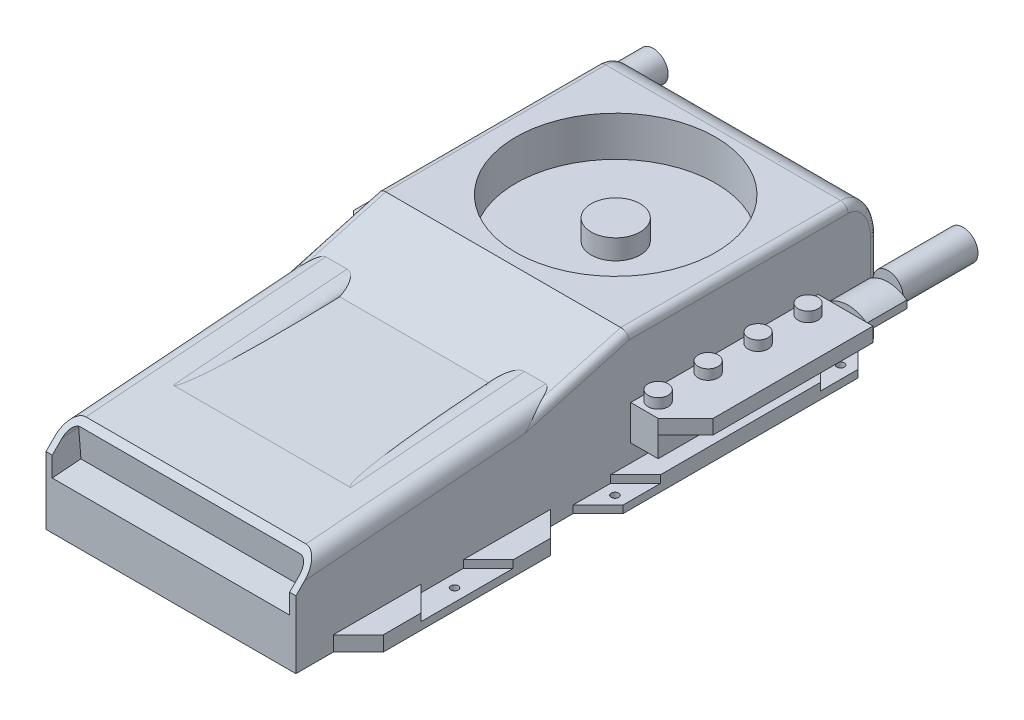
SolidWorks part; units mm, degrees
note: The reader was unsure of these and kept them because the rebuilt part matched: shared geometry of "Sketch10<3>".
ref_plane "Front Plane" through (0, 0, 0) normal (0, 0, 1) x (1, 0, 0)
ref_plane "Top Plane" through (0, 0, 0) normal (0, 1, 0) x (1, 0, 0)
ref_plane "Right Plane" through (0, 0, 0) normal (1, 0, 0) x (0, 0, -1)
sketch "Sketch1" plane through (0, 0, 0) normal (1, 0, 0) x (0, 0, -1)
  line L0 (-116.5, 8.5) -> (-106.5, 18.5)
  line L1 (-116.5, -18.5) -> (116.5, -18.5)
  line L2 (-116.5, -18.5) -> (-116.5, 18.5)
  line L3 (-116.5, 18.5) -> (116.5, 18.5)
  line L4 (116.5, -18.5) -> (116.5, 18.5)
  line L5 (-116.5, -18.5) -> (116.5, 18.5) construction
  line L6 (-116.5, 18.5) -> (116.5, -18.5) construction
  line L7 (-106.5, 18.5) -> (-10.5, 26)
  line L8 (-10.5, 26) -> (16.5, 33.5)
  line L9 (16.5, 33.5) -> (116.5, 33.5)
  line L10 (116.5, 33.5) -> (116.5, 18.5)
  point P0 (0, 0)
  dimension "D1" = 233
  dimension "D2" = 37
  dimension "D3" = 10
  dimension "D4" = 10
  dimension "D5" = 96
  dimension "D6" = 44.5
  dimension "D7" = 27
  dimension "D8" = 52
extrude "Boss-Extrude1" add sketch "Sketch1" along normal mid plane 100 contours L1 L4 L3 L0 L2 | L10 L9 L8 L7 L3
fillet "Fillet1" radius 12 1 edges at (0, 33.5, -116.5)
sketch "Sketch2" plane through (0, 33.5, 0) normal (0, 1, 0) x (1, 0, 0)
  line L0 (0, 61.5) -> (0, 0) construction
  line L1 (-50, 116.5) -> (50, 116.5) construction
  circle A0 centre (0, 61.5) radius 40
  dimension "D2" = 80
  dimension "D1" = 55
extrude "Cut-Extrude1" cut sketch "Sketch2" against normal blind 16
ref_plane "Plane1" through (0, -9.1586, 117.2298) normal (0, 0.0779, -0.997) x (-1, 0, 0)
sketch "Sketch5" plane through (0, -9.1586, 117.2298) normal (0, 0.0779, -0.997) x (-1, 0, 0)
  line L0 (0, 17.1301) -> (0, 0) construction
  line L1 (47.5, 9.6301) -> (-47.5, 9.6301)
  line L2 (47.5, 9.6301) -> (47.5, 24.6301)
  line L3 (47.5, 24.6301) -> (-47.5, 24.6301)
  line L4 (-47.5, 9.6301) -> (-47.5, 24.6301)
  line L5 (47.5, 9.6301) -> (-47.5, 24.6301) construction
  line L6 (47.5, 24.6301) -> (-47.5, 9.6301) construction
  line L7 (-50, -9.3699) -> (50, -9.3699) construction
  line L8 (-50, -9.3699) -> (-50, 17.5481) construction
  point P0 (0, 17.1301)
  point P7 (-0.6176, 3.5002)
  point P8 (0, 0)
  point P9 (0, 0)
  dimension "D1" = 19
  dimension "D2" = 15
  dimension "D3" = 2.5
extrude "Cut-Extrude4" cut sketch "Sketch5" along normal blind 13
sketch "Sketch6" plane through (0, 0, 0) normal (1, 0, 0) x (0, 0, -1)
  line L0 (-80.0964, 20.5628) -> (-19.1717, 23.5912)
  line L1 (-106.5, 18.5) -> (-10.5, 26) construction
  line L2 (-19.1717, 23.5912) -> (-10.5, 26)
  line L4 (-80.0964, 20.5628) -> (-10.5, 26)
  line L5 (-10.5, 26) -> (16.5, 33.5) construction
  point P5 (-11.0444, 25.9575)
  dimension "D1" = 9
  dimension "D2" = 61
extrude "Cut-Extrude5" cut sketch "Sketch6" against normal mid plane 59 contours L4 L0 L2
fillet "Fillet2" radius 6 2 edges at (-50, 22.25, 58.5) (50, 22.25, 58.5)
fillet "Fillet3" radius 3.5 2 edges at (-47.5, 16.3074, 107.491) (47.5, 16.3074, 107.491)
fillet "Fillet4" radius 3 8 edges at (-50, 25.5634, 12.0719) (50, 25.5634, 12.0719)
fillet "Fillet5" radius 2.41 1 edges at (-29.5, 23.2814, 45.2982)
fillet "Fillet6" radius 2.41 1 edges at (29.5, 23.2814, 45.2982)
sketch "Sketch7" plane through (0, -18.5, 0) normal (0, -1, 0) x (1, 0, 0)
  line L0 (-50, 101.5) -> (-60, 91.5)
  line L1 (-50, 116.5) -> (-50, -113.5) construction
  line L2 (-60, 91.5) -> (-60, 24.5)
  line L3 (-60, 24.5) -> (-50, 14.5)
  line L4 (-50, 5.5) -> (-60, -4.5)
  line L5 (-60, -4.5) -> (-60, -98.5)
  line L6 (-60, -98.5) -> (-50, -108.5)
  line L7 (47, -116.5) -> (-47, -116.5) construction
  line L8 (-50, 101.5) -> (-50, 14.5)
  line L9 (-50, 5.5) -> (-50, -108.5)
  point P8 (-50, -113.5)
  point P11 (-309.5825, -21.0482)
  point P13 (-297.7358, -62.1311)
  point P14 (-50, -113.5)
  point P15 (-50, -113.5)
  point P16 (-50, -107.5715)
  dimension "D1" = 10
  dimension "D2" = 94
  dimension "D3" = 67
  dimension "D4" = 9
  dimension "D5" = 8
extrude "Boss-Extrude2" add sketch "Sketch7" against normal blind 6
sketch "Sketch8" plane through (0, -18.5, 0) normal (0, -1, 0) x (1, 0, 0)
  line L0 (-55, -96.5) -> (-55, -6.2108) construction
  line L1 (-55, 0.7892) -> (-55, 19.5) construction
  line L3 (-60, -4.5) -> (-60, -98.5) construction
  line L4 (-55, -96.5) -> (-55, -103.5) construction
  line L7 (-55, -6.2108) -> (-55, 0.7892) construction
  line L10 (-55, 19.5) -> (-55, 58) construction
  line L11 (-55, 58) -> (-55, 96.5) construction
  line L12 (-50, 101.5) -> (-60, 91.5) construction
  circle A0 centre (-55, 58) radius 1.5
  circle A1 centre (-55, -6.2108) radius 1.5
  circle A2 centre (-55, -96.5) radius 1.5
  dimension "D1" = 3
  dimension "D2" = 5
  dimension "D3" = 7
extrude "Cut-Extrude6" cut sketch "Sketch8" against normal through all
sketch "Sketch9" plane through (0, -12.5, 0) normal (0, 1, 0) x (1, 0, 0)
  line L0 (-60, 83.5) -> (-50, 93.5)
  line L1 (-60, 4.5) -> (-60, 98.5) construction
  line L2 (-50, 16.9089) -> (-50, 104.5) construction
  line L3 (-60, 19.5) -> (-50, 9.5)
  line L4 (-50, 108.5) -> (-50, -5.5) construction
  line L5 (-50, -5.5) -> (-60, 4.5) construction
  line L6 (-60, 98.5) -> (-50, 108.5) construction
  line L7 (-50, 108.5) -> (-50, 93.5)
  line L8 (-50, 9.5) -> (-50, -5.5)
  line L9 (-50, -5.5) -> (-60, 4.5)
  line L10 (-60, 98.5) -> (-50, 108.5)
  line L11 (-60, 4.5) -> (-60, 19.5)
  line L12 (-60, 83.5) -> (-60, 98.5)
  line L13 (-60, -39.5) -> (-50, -49.5)
  line L14 (-60, -91.5) -> (-60, -24.5) construction
  line L15 (-50, -14.5) -> (-50, -101.5) construction
  line L16 (-60, -76.5) -> (-50, -66.5)
  line L17 (-50, -113.0283) -> (-50, -25.0487) construction
  line L18 (-60, -24.5) -> (-50, -14.5) construction
  line L19 (-50, -101.5) -> (-60, -91.5) construction
  line L20 (-60, -76.5) -> (-60, -39.5)
  line L21 (-50, -49.5) -> (-50, -66.5)
  line L22 (-55, -58) -> (-50, -58) construction
  circle A0 centre (-55, -58) radius 1.5 construction
  circle A1 centre (-55, -58) radius 1.5 construction
  dimension "D1" = 15
  dimension "D2" = 37
extrude "Cut-Extrude7" cut sketch "Sketch9" against normal offset from surface (3 mm away) 3 up to face at (-55, -18.5, 56.5)
mirror "Mirror1" about plane through (0, 0, 0) normal (1, 0, 0) of "Boss-Extrude2", "Cut-Extrude6", "Cut-Extrude7"
ref_plane "Plane2" through (0, 8.5, 0) normal (0, 1, 0) x (1, 0, 0)
sketch "Sketch10" plane through (0, 8.5, 0) normal (0, 1, 0) x (1, 0, 0)
  line L0 (-50, 92.5) -> (-50, 17.5)
  line L1 (-50, 93.5) -> (-50, 9.5) construction
  line L2 (-50, 92.5) -> (-72, 92.5)
  line L3 (-72, 92.5) -> (-72, 28.5)
  line L4 (-72, 28.5) -> (-61, 17.5)
  line L5 (-61, 17.5) -> (-50, 17.5)
  line L6 (-47, 116.5) -> (47, 116.5) construction
  line L7 (-61, 17.5) -> (-61, 92.5)
  dimension "D1" = 45
  dimension "D2" = 22
  dimension "D3" = 11
  dimension "D4" = 64
  dimension "D5" = 24
extrude "Boss-Extrude3" add sketch "Sketch10" against normal blind 14 contours L7 L5 L0 L2
extrude "Boss-Extrude4" add sketch "Sketch10<3>" against normal blind 5.75 contours L4 L7 L2 L3
sketch "Sketch10<3>" plane through (0, 8.5, 0) normal (0, 1, 0) x (1, 0, 0) same geometry as "Sketch10"
sketch "Sketch11" plane through (0, 8.5, 0) normal (0, 1, 0) x (1, 0, 0)
  line L0 (-61, 17.5) -> (-50, 17.5) construction
  line L1 (-50, 92.5) -> (-50, 17.5) construction
  circle A0 centre (-55, 23.5) radius 4
  dimension "D1" = 8
  dimension "D2" = 6
  dimension "D3" = 5
extrude "Boss-Extrude5" add sketch "Sketch11" along normal blind 4
pattern_linear "LPattern1" count 4 spacing 20 along (0, 0, -1) of "Boss-Extrude5"
sketch "Sketch12" plane through (0, 0, -92.5) normal (0, 0, -1) x (-1, 0, 0)
  line L0 (61, 2.75) -> (72, 2.75) construction
  line L1 (54.5, 5.25) -> (69.5, 5.25)
  line L2 (54.5, 5.25) -> (54.5, 8.25)
  line L3 (54.5, 8.25) -> (69.5, 8.25)
  line L4 (69.5, 5.25) -> (69.5, 8.25)
  line L5 (54.5, 5.25) -> (69.5, 8.25) construction
  line L6 (54.5, 8.25) -> (69.5, 5.25) construction
  line L7 (72, 2.75) -> (72, 8.5) construction
  arc A0 (54.5, 8.25) -> (69.5, 8.25) centre (62, -1.75) cw
  arc A1 (54.5, 5.25) -> (69.5, 5.25) centre (62, 15.25) ccw
  point P0 (62, 6.75)
  point P7 (62, 10.75)
  point P8 (62, 2.75)
  line M6 (72, 8.5) -> (50, 8.5)
  dimension "D1" = 15
  dimension "D2" = 8
  dimension "D3" = 3
  dimension "D4" = 10
extrude "Boss-Extrude6" add sketch "Sketch12" along normal blind 16 contours L1 L4 L3 L2 | A0 M6 | A0 L3 M6 | L1 A1
sketch "Sketch13" plane through (0, 0, -108.5) normal (0, 0, -1) x (-1, 0, 0)
  line L0 (62, 8.75) -> (54.5, 8.75) construction
  line L1 (54.5, 8.75) -> (54.5, 8.25) construction
  line L2 (62, 8.75) -> (69.5, 8.75) construction
  line L3 (69.5, 8.75) -> (69.5, 8.25) construction
  arc A0 (54.5, 5.25) -> (69.5, 5.25) centre (62, 15.25) ccw construction
  arc A1 (54.5, 5.25) -> (69.5, 5.25) centre (62, 15.25) ccw
  circle A2 centre (62, 8.75) radius 6
  arc M7 (69.5, 8.25) -> (54.5, 8.25) centre (62, -1.75) ccw
  dimension "D1" = 12
extrude "Boss-Extrude7" add sketch "Sketch13" along normal blind 30 contours A2 M7 | A2 M7
mirror "Mirror2" about plane through (0, 0, 0) normal (1, 0, 0) of "Boss-Extrude3", "Boss-Extrude4", "Boss-Extrude5", "LPattern1", "Boss-Extrude6", "Boss-Extrude7"
sketch "Sketch14" plane through (0, 17.5, 0) normal (0, 1, 0) x (1, 0, 0)
  circle A0 centre (0, 61.5) radius 40 construction
  circle A1 centre (0, 61.5) radius 40
  circle A2 centre (0, 61.5) radius 9.8055
extrude "Boss-Extrude8" add sketch "Sketch14" along normal blind 8 contours A2
